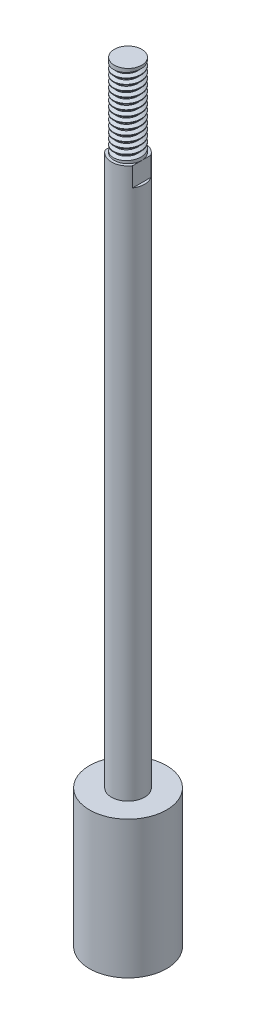
SolidWorks part; units mm, degrees
ref_plane "Front Plane" through (0, 0, 0) normal (0, 0, 1) x (1, 0, 0)
ref_plane "Top Plane" through (0, 0, 0) normal (0, 1, 0) x (1, 0, 0)
ref_plane "Right Plane" through (0, 0, 0) normal (1, 0, 0) x (0, 0, -1)
sketch "Sketch1" plane through (0, 0, 0) normal (0, 1, 0) x (1, 0, 0)
  circle A0 centre (0, 0) radius 3
  dimension "D1" = 6
extrude "Boss-Extrude1" add sketch "Sketch1" along normal blind 115
sketch "Sketch2" plane through (0, 0, 0) normal (0, -1, 0) x (1, 0, 0)
  circle A0 centre (0, 0) radius 7
extrude "Boss-Extrude2" add sketch "Sketch2" along normal blind 25 separate body
sketch "Sketch3" plane through (0, 115, 0) normal (0, 1, 0) x (1, 0, 0)
  circle A0 centre (0, 0) radius 2.5
  circle A1 centre (0, 0) radius 3
extrude "Cut-Extrude2" cut sketch "Sketch3" against normal blind 15
thread "Thread1" pitch 1 method cut profile "Thread Profile1" start angle 0, offset 0, length 14, pitch 1, diameter 5
ref_plane "Plane1" through (-2.5, 115, 0) normal (0, 0, 1) x (-1, 0, 0)
sketch "Thread Profile1" plane through (-2.5, 115, 0) normal (0, 0, 1) x (-1, 0, 0)
  line L0 (0, 0) -> (0, 1) construction
  line L11 (0, 0) -> (0, 0.875)
  line L12 (0, 0.875) -> (-0.5413, 0.5625)
  line L13 (-0.5413, 0.5625) -> (-0.5413, 0.3125)
  line L15 (-0.5413, 0.3125) -> (0, 0)
  line L17 (-0.5413, 0.4375) -> (0, 0.4375) construction
  point P2 (0, 0)
  dimension "Pitch" = 1
  dimension "Profile_Angle" = 60
  dimension "Profile_Land" = 0.25
  dimension "Profile_Height" = 0.5413
sketch "Sketch6" plane through (0, 100, 0) normal (0, 1, 0) x (1, 0, 0)
  line L2 (-2.5, 2.4822) -> (-3.8345, 2.4822)
  line L3 (-2.5, 2.4822) -> (-2.5, -2.1858)
  line L4 (-2.5, -2.1858) -> (-3.8345, -2.1858)
  line L5 (-3.8345, 2.4822) -> (-3.8345, -2.1858)
  line L6 (2.5, 2.4822) -> (3.7218, 2.4822)
  line L7 (2.5, 2.4822) -> (2.5, -2.1858)
  line L8 (2.5, -2.1858) -> (3.7218, -2.1858)
  line L9 (3.7218, 2.4822) -> (3.7218, -2.1858)
  point P6 (0, 0)
extrude "Cut-Extrude3" cut sketch "Sketch6" against normal blind 3.5
